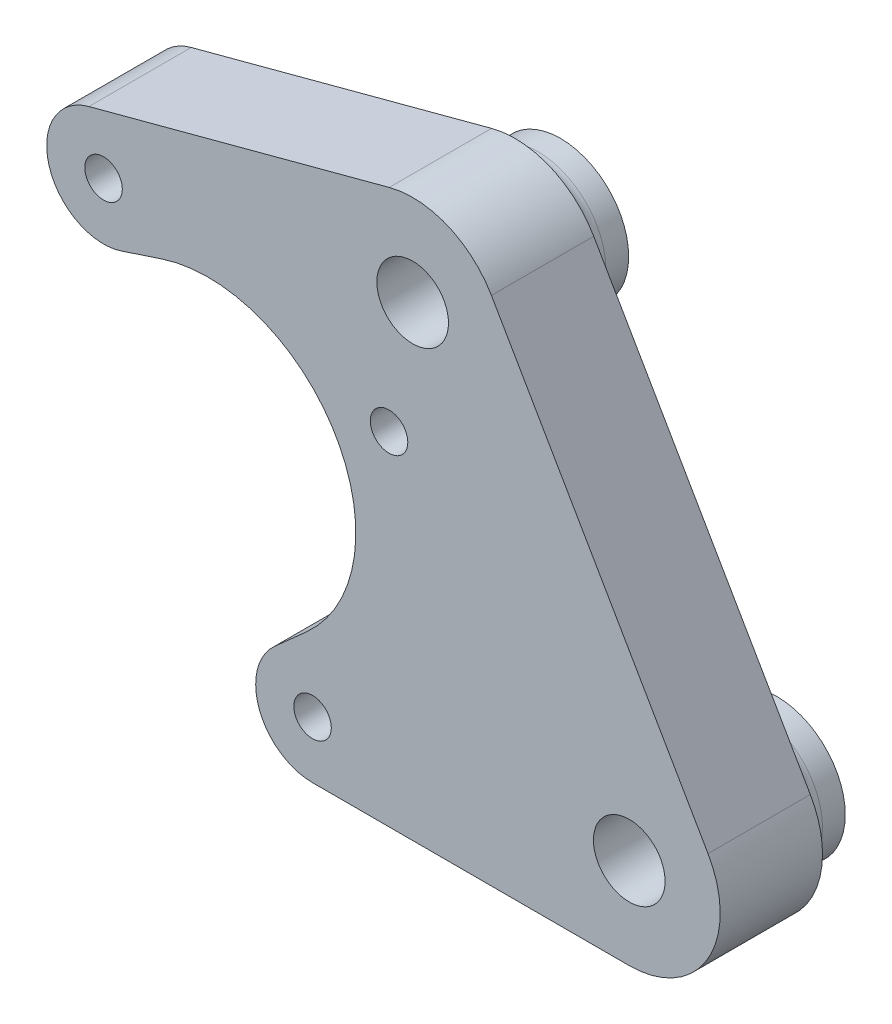
SolidWorks part; units mm, degrees
ref_plane "Front Plane" through (0, 0, 0) normal (0, 0, 1) x (1, 0, 0)
ref_plane "Top Plane" through (0, 0, 0) normal (0, 1, 0) x (1, 0, 0)
ref_plane "Right Plane" through (0, 0, 0) normal (1, 0, 0) x (0, 0, -1)
sketch "Sketch1" plane through (0, 0, 0) normal (0, 0, 1) x (1, 0, 0)
  line L0 (18, 20.07) -> (37.0525, -12.9299) construction
  line L1 (15.9217, 9.1924) -> (-9.1924, 15.9217) construction
  line L2 (-9.1924, 15.9217) -> (-15.9217, -9.1924) construction
  line L3 (-15.9217, -9.1924) -> (9.1924, -15.9217) construction
  line L4 (9.1924, -15.9217) -> (15.9217, 9.1924) construction
  line L5 (0, 0) -> (50.7667, 0) construction
  line L6 (0, 0) -> (-9.1924, 15.9217) construction
  line L7 (-4.0727, 12.3456) -> (-7.626, 11.1734)
  line L8 (8.6552, -9.6998) -> (5.8634, -12.191)
  line L9 (0, 0) -> (9.1924, -15.9217) construction
  line L10 (15.9382, 27.7997) -> (-10.481, 20.7528)
  line L11 (24.9282, 24.07) -> (43.9807, -8.9299)
  line L12 (37.0501, -20.9299) -> (9.1909, -20.9217)
  arc A0 (8.6552, -9.6998) -> (-4.0727, 12.3456) centre (0, 0) ccw
  circle A1 centre (18, 20.07) radius 3.15
  circle A2 centre (-9.1924, 15.9217) radius 1.65
  circle A3 centre (15.9217, 9.1924) radius 1.65
  circle A4 centre (9.1924, -15.9217) radius 1.65
  circle A6 centre (37.0525, -12.9299) radius 3.15
  arc A7 (-10.481, 20.7528) -> (-7.626, 11.1734) centre (-9.1924, 15.9217) ccw
  arc A8 (24.9282, 24.07) -> (15.9382, 27.7997) centre (18, 20.07) ccw
  arc A9 (37.0501, -20.9299) -> (43.9807, -8.9299) centre (37.0525, -12.9299) ccw
  arc A10 (5.8634, -12.191) -> (9.1909, -20.9217) centre (9.1924, -15.9217) ccw
  dimension "D1" = 26
  dimension "D2" = 3.3
  dimension "D3" = 6.3
  dimension "D9" = 5
  dimension "D10" = 8
  dimension "D4" = 20.07
  dimension "D5" = 38.105
  dimension "D6" = 60
  dimension "D7" = 18
  dimension "D8" = 15
extrude "Boss-Extrude1" add sketch "Sketch1" along normal blind 9
sketch "Sketch2" plane through (0, 0, 0) normal (0, 0, -1) x (-1, 0, 0)
  line L0 (-9.1924, -15.9217) -> (-15.9217, 9.1924) construction
  line L1 (8.0466, 20.584) -> (-17.2606, 13.803)
  line L2 (-20.584, 8.0466) -> (-13.803, -17.2606)
  line L5 (-17.2606, 13.803) -> (-20.584, 8.0466)
  line L6 (22.3804, 12.3084) -> (8.0466, 20.584)
  line L8 (-13.803, -17.2606) -> (9.2595, -30.5757)
  line L9 (22.3804, 12.3084) -> (9.2595, -30.5757)
  line L11 (20.584, -8.0466) -> (13.803, 17.2606) [skipped]
  line L12 (-8.0466, -20.584) -> (17.2606, -13.803) [skipped]
  circle A0 centre (0, 0) radius 17.8 construction
  circle A1 centre (0, 0) radius 21.8496 construction
  circle A2 centre (-18, 20.07) radius 6 construction
  circle A3 centre (-18, 20.07) radius 3.15 construction
  point P2 (6.5153, 24.3153)
  point P3 (-21.8005, 12.5865)
  point P4 (-6.5153, -24.3153)
  point P5 (24.3153, -6.5153)
  dimension "D1" = 35.6
  dimension "D2" = 12
  dimension "D4" = 4.7
extrude "Cut-Extrude1" cut sketch "Sketch2" against normal offset from surface (3 mm away) 6 up to face at (21.15, 20.07, 9)
sketch "Sketch3" plane through (0, 0, 0) normal (0, 0, -1) x (-1, 0, 0)
  circle A0 centre (-18, 20.07) radius 6
  circle A1 centre (-18, 20.07) radius 3.15
  circle A2 centre (-37.0525, -12.9299) radius 3.15
  circle A3 centre (-37.0525, -12.9299) radius 6
  dimension "D1" = 12
extrude "Boss-Extrude2" add sketch "Sketch3" along normal blind 4
fillet "Fillet1" radius 2 2 edges at (24, 20.07, 0) (43.0525, -12.9299, 0)
